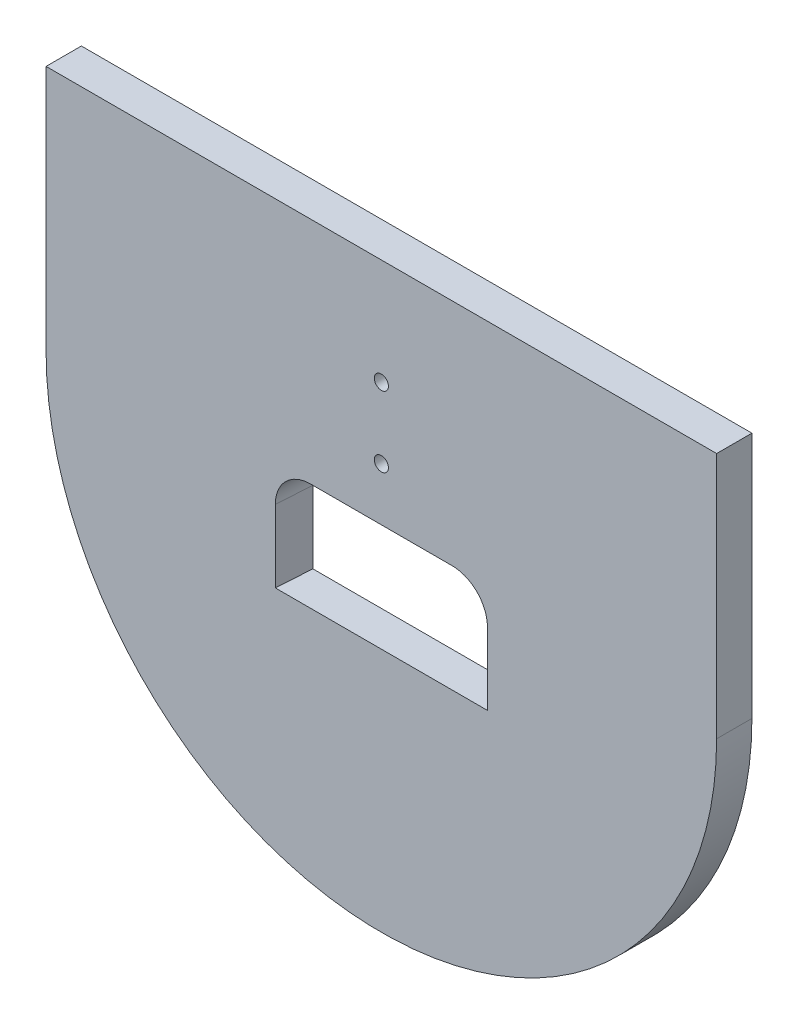
SolidWorks part; units mm, degrees
ref_plane "Front Plane" through (0, 0, 0) normal (0, 0, 1) x (1, 0, 0)
ref_plane "Top Plane" through (0, 0, 0) normal (0, 1, 0) x (1, 0, 0)
ref_plane "Right Plane" through (0, 0, 0) normal (1, 0, 0) x (0, 0, -1)
sketch "Sketch1" plane through (0, 0, 0) normal (0, 0, 1) x (1, 0, 0)
  line L0 (0, -70) -> (0, 0)
  line L1 (0, 0) -> (-190, 0)
  line L2 (-190, 0) -> (-190, -70)
  line L4 (-124.4, -65) -> (-65.6, -65)
  line L5 (-124.4, -65) -> (-124.4, -95.5)
  line L6 (-124.4, -95.5) -> (-65.6, -95.5)
  line L7 (-65.6, -65) -> (-65.6, -95.5)
  circle A1 centre (-95, -50) radius 2
  circle A2 centre (-95, -30) radius 2
  arc A4 (-190, -70) -> (0, -70) centre (-95, -70) ccw
  point P6 (-95, -65)
  point P11 (-95, 0)
  dimension "D1" = 65.6
  dimension "D6" = 4
  dimension "D7" = 20
  dimension "D8" = 15
  dimension "D9" = 95
  dimension "D2" = 70
  dimension "D3" = 58.8
  dimension "D4" = 30.5
  dimension "D5" = 65
extrude "Boss-Extrude1" add sketch "Sketch1" along normal blind 10
chamfer "Chamfer1" distance 10 angle 3.71 2 edges at (-65.6, -80.25, 10) (-124.4, -80.25, 10) first distance on face at (-65.6, -80.25, 5) first distance on face at (-124.4, -80.25, 5)
fillet "Fillet1" radius 10 2 edges at (-124.7242, -65, 5) (-65.2758, -65, 5)
